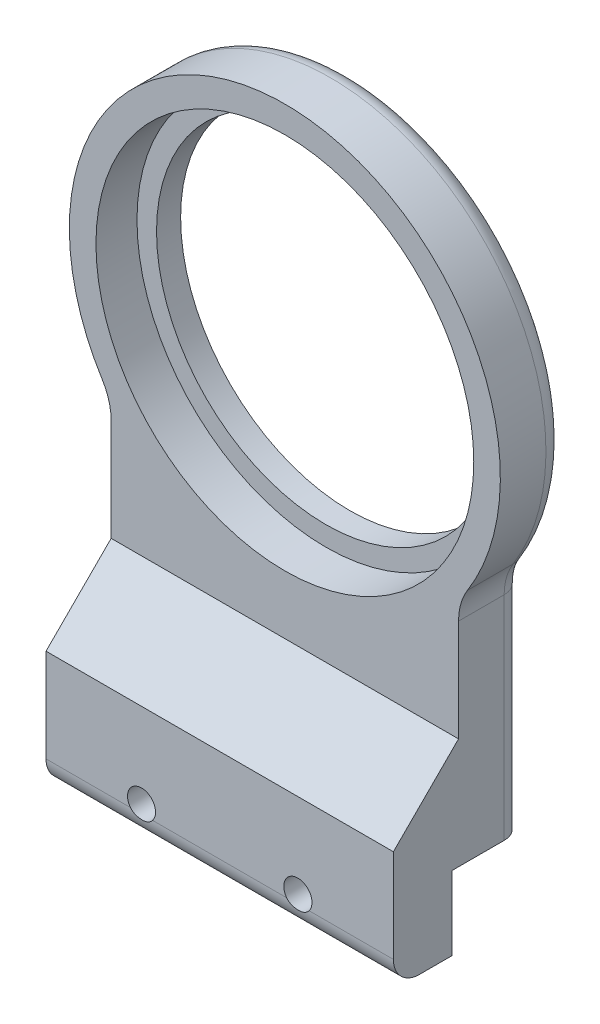
SolidWorks part; units mm, degrees
ref_plane "前视基准面" through (0, 0, 0) normal (0, 0, 1) x (1, 0, 0)
ref_plane "上视基准面" through (0, 0, 0) normal (0, 1, 0) x (1, 0, 0)
ref_plane "右视基准面" through (0, 0, 0) normal (1, 0, 0) x (0, 0, -1)
other "Configuration Table"
sketch "草图1" plane through (0, 0, 0) normal (0, 0, 1) x (1, 0, 0)
  line L0 (0, 27.158) -> (0, -27.842) construction
  line L1 (26.6642, -27.842) -> (-26.6642, -27.842)
  line L2 (26.6642, -27.842) -> (26.6642, 7.5741)
  line L4 (-26.6642, -27.842) -> (-26.6642, 7.5741)
  arc A0 (26.6642, 7.5741) -> (-26.6642, 7.5741) centre (0, 27.158) ccw
  circle A1 centre (0, 27.158) radius 26
  point P0 (0, 0)
  point P22 (0, 27.158)
extrude "凸台-拉伸1" add sketch "草图1" along normal blind 10
sketch "草图3" plane through (0, 0, 10) normal (0, 0, 1) x (1, 0, 0)
  circle A0 centre (0, 27.158) radius 29
extrude "切除-拉伸1" cut sketch "草图3" against normal blind 6.3
fillet "圆角1" radius 9 2 edges at (-26.6642, 7.5741, 5) (26.6642, 7.5741, 5)
sketch "草图4" plane through (0, 0, 10) normal (0, 0, 1) x (1, 0, 0)
  line L1 (-26.6642, -27.842) -> (26.6642, -27.842)
  line L2 (-26.6642, -27.842) -> (-26.6642, -39.158)
  line L3 (-26.6642, -39.158) -> (26.6642, -39.158)
  line L4 (26.6642, -27.842) -> (26.6642, -39.158)
extrude "凸台-拉伸2" add sketch "草图4" along normal blind 10 separate body
sketch "草图5" plane through (0, 0, 10) normal (0, 0, -1) x (-1, 0, 0)
  line L1 (-26.6642, -27.842) -> (26.6642, -27.842)
  line L2 (-26.6642, -27.842) -> (-26.6642, -39.158)
  line L3 (-26.6642, -39.158) -> (26.6642, -39.158)
  line L4 (26.6642, -27.842) -> (26.6642, -39.158)
extrude "凸台-拉伸3" add sketch "草图5" along normal blind 2
sketch "草图6" plane through (0, -27.842, 0) normal (0, 1, 0) x (1, 0, 0)
  line L1 (-26.6642, -10) -> (26.6642, -10)
  line L2 (-26.6642, -10) -> (-26.6642, -20)
  line L3 (-26.6642, -20) -> (26.6642, -20)
  line L4 (26.6642, -10) -> (26.6642, -20)
extrude "凸台-拉伸4" add sketch "草图6" along normal blind 3
chamfer "倒角1" distance 14 angle 45 1 edges at (0, -24.842, 10)
fillet "圆角3" radius 3 5 edges at (-26.6642, -11.512, 0) (-27.0142, 7.3035, 0) (26.6642, -11.512, 0) (27.0142, 7.3035, 0) (0, 60.2414, 0)
sketch "草图7" plane through (0, 0, 8) normal (0, 0, -1) x (-1, 0, 0)
  line L0 (0, -27.842) -> (0, -33.842) construction
  line L1 (23.6642, -27.842) -> (-23.6642, -27.842) construction
  line L2 (0, -33.842) -> (-12, -33.842) construction
  line L3 (0, -33.842) -> (12, -33.842) construction
  circle A0 centre (-12, -33.842) radius 1.7
  circle A1 centre (12, -33.842) radius 1.7
extrude "切除-拉伸2" cut sketch "草图7" against normal blind 14
sketch "草图8" plane through (0, 0, 20) normal (0, 0, 1) x (1, 0, 0)
  line L0 (-12, -20.842) -> (-12, -33.842) construction
  line L1 (26.6642, -20.842) -> (-26.6642, -20.842) construction
  line L2 (12, -20.842) -> (12, -33.842) construction
  circle A0 centre (-12, -33.842) radius 2.15
  circle A1 centre (12, -33.842) radius 2.165
extrude "切除-拉伸3" cut sketch "草图8" against normal blind 6
sketch "草图9" plane through (0, 0, 8) normal (0, 0, -1) x (-1, 0, 0)
  line L0 (-26.6642, -39.158) -> (26.6642, -39.158) construction
  line L1 (-26.6642, -27.842) -> (26.6642, -27.842)
  line L2 (-26.6642, -27.842) -> (-26.6642, -39.158)
  line L3 (-26.6642, -39.158) -> (26.6642, -39.158)
  line L4 (26.6642, -27.842) -> (26.6642, -39.158)
extrude "切除-拉伸4" cut sketch "草图9" against normal blind 3
fillet "圆角4" radius 4 1 edges at (0, -39.158, 20)
